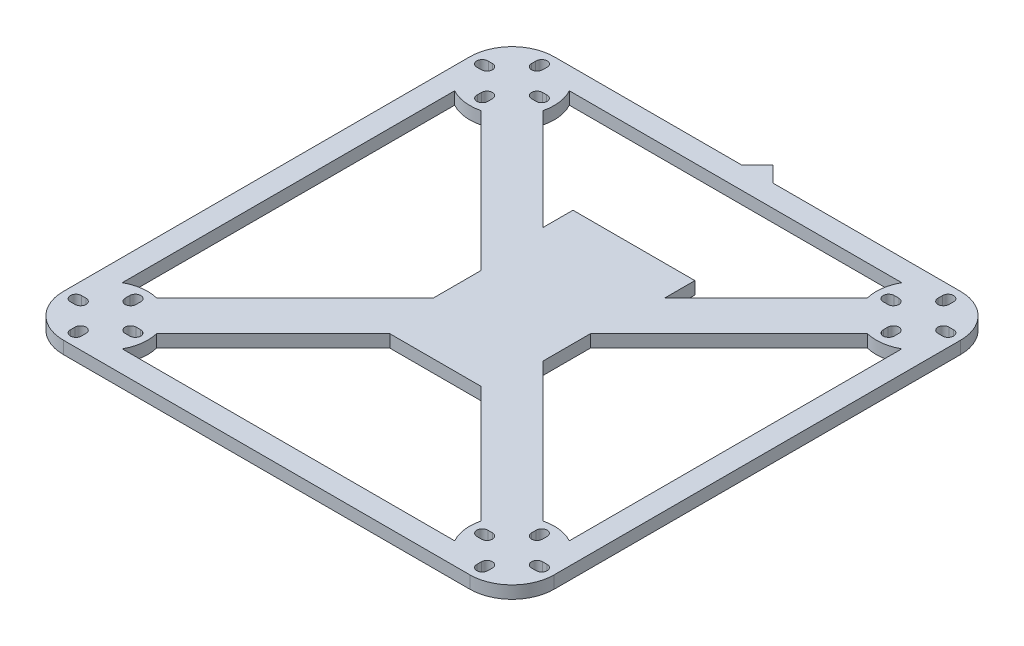
SolidWorks part; units mm, degrees
ref_plane "Front Plane" through (0, 0, 0) normal (0, 0, 1) x (1, 0, 0)
ref_plane "Top Plane" through (0, 0, 0) normal (0, 1, 0) x (1, 0, 0)
ref_plane "Right Plane" through (0, 0, 0) normal (1, 0, 0) x (0, 0, -1)
sketch "Sketch1" plane through (0, 0, 0) normal (0, 1, 0) x (1, 0, 0)
  line L0 (0, 78.5) -> (0, -78.5) construction
  line L1 (-78.5, 78.5) -> (78.5, 78.5)
  line L2 (-78.5, 78.5) -> (-78.5, -78.5)
  line L3 (-78.5, -78.5) -> (78.5, -78.5)
  line L4 (78.5, 78.5) -> (78.5, -78.5)
  line L5 (-78.5, 78.5) -> (78.5, -78.5) construction
  line L6 (-78.5, -78.5) -> (78.5, 78.5) construction
  line L7 (78.5, 0) -> (-78.5, 0) construction
  line L8 (-1, 65) -> (-1, 0) construction
  line L9 (-83.4497, 73.5503) -> (73.5503, -83.4497)
  line L10 (-73.5503, 83.4497) -> (83.4497, -73.5503)
  line L11 (-73.5503, -83.4497) -> (83.4497, 73.5503)
  line L12 (-83.4497, -73.5503) -> (73.5503, 83.4497)
  line L13 (-53.1678, 71.5) -> (53.1678, 71.5)
  line L14 (-53.1678, -71.5) -> (53.1678, -71.5)
  line L15 (71.5, -53.1678) -> (71.5, 53.1678)
  line L16 (-71.5, -53.1678) -> (-71.5, 53.1678)
  circle A0 centre (-65, 65) radius 13.5
  circle A1 centre (-65, 65) radius 64
  circle A2 centre (65, 65) radius 13.5
  circle A3 centre (-65, -65) radius 13.5
  circle A4 centre (65, -65) radius 13.5
  point P0 (0, 0)
  dimension "D1" = 27
  dimension "D2" = 128
  dimension "D3" = 2
  dimension "D4" = 14
  dimension "D5" = 7
extrude "Base shape" add sketch "Sketch1" along normal blind 4 contours L12 A3 L11 L9 | A4 L10 L11 L9 | L11 A2 L12 L10 | L9 A1 L10 A0 | A1 L9 L12 L10 | L12 L9 L11 L10 | L13 A1 L1 A0 | L13 A2 L1 A1 | A4 L4 A2 L15 | A4 L14 A3 L3 | L2 A3 L16 A1 | L2 A1 L16 A0 | A0 | A2 | A4 | A3 region at (-29.268, 0, -75.0845) region at (-75.0845, 0, -29.268) region at (27.4447, 0, -75.1014) region at (-37.8705, 0, -37.8705) region at (-75.1014, 0, 27.4447) region at (-12.3929, 0, -12.3929) region at (30.427, 0, -30.427) region at (0, 0, 0) region at (-30.427, 0, 30.427) region at (30.427, 0, 30.427) region at (75.0932, 0, 0) region at (0, 0, 75.0932)
sketch "Sketch2" plane through (0, 4, 0) normal (0, 1, 0) x (1, 0, 0)
  line L0 (-65, 74.5) -> (-65, 55.5) construction
  line L1 (-74.5, 65) -> (-55.5, 65) construction
  line L2 (0, 78.5) -> (0, -78.5) construction
  line L3 (-65, 78.5) -> (65, 78.5) construction
  line L4 (-65, -78.5) -> (65, -78.5) construction
  line L5 (-78.5, 0) -> (78.5, 0) construction
  line L6 (-78.5, 65) -> (-78.5, -65) construction
  line L7 (78.5, 65) -> (78.5, -65) construction
  line L8 (-66.75, 74.5) -> (-66.75, 73)
  line L9 (-63.25, 74.5) -> (-63.25, 73)
  line L10 (-74.5, 66.75) -> (-73, 66.75)
  line L11 (-74.5, 63.25) -> (-73, 63.25)
  line L12 (-66.75, 57) -> (-66.75, 55.5)
  line L13 (-63.25, 57) -> (-63.25, 55.5)
  line L14 (-57, 66.75) -> (-55.5, 66.75)
  line L15 (-57, 63.25) -> (-55.5, 63.25)
  line L16 (63.25, 57) -> (63.25, 55.5)
  line L17 (66.75, 57) -> (66.75, 55.5)
  line L18 (74.5, 63.25) -> (73, 63.25)
  line L19 (74.5, 66.75) -> (73, 66.75)
  line L20 (63.25, 74.5) -> (63.25, 73)
  line L21 (66.75, 74.5) -> (66.75, 73)
  line L22 (57, 66.75) -> (55.5, 66.75)
  line L23 (57, 63.25) -> (55.5, 63.25)
  line L24 (-66.75, -57) -> (-66.75, -55.5)
  line L25 (-63.25, -57) -> (-63.25, -55.5)
  line L26 (-57, -63.25) -> (-55.5, -63.25)
  line L27 (-57, -66.75) -> (-55.5, -66.75)
  line L28 (-74.5, -63.25) -> (-73, -63.25)
  line L29 (-74.5, -66.75) -> (-73, -66.75)
  line L30 (-63.25, -74.5) -> (-63.25, -73)
  line L31 (-66.75, -74.5) -> (-66.75, -73)
  line L32 (57, -63.25) -> (55.5, -63.25)
  line L33 (57, -66.75) -> (55.5, -66.75)
  line L34 (66.75, -74.5) -> (66.75, -73)
  line L35 (63.25, -74.5) -> (63.25, -73)
  line L36 (74.5, -66.75) -> (73, -66.75)
  line L37 (74.5, -63.25) -> (73, -63.25)
  line L38 (66.75, -57) -> (66.75, -55.5)
  line L39 (63.25, -57) -> (63.25, -55.5)
  circle A0 centre (-65, 65) radius 9.5
  circle A1 centre (-65, 65) radius 8
  circle A2 centre (-65, 74.5) radius 1.75
  circle A3 centre (-65, 55.5) radius 1.75
  circle A4 centre (-57, 65) radius 1.75
  circle A5 centre (-73, 65) radius 1.75
  circle A6 centre (-65, 73) radius 1.75
  circle A7 centre (-55.5, 65) radius 1.75
  circle A8 centre (-74.5, 65) radius 1.75
  circle A9 centre (-65, 57) radius 1.75
  circle A10 centre (65, 57) radius 1.75
  circle A11 centre (65, 55.5) radius 1.75
  circle A12 centre (73, 65) radius 1.75
  circle A13 centre (74.5, 65) radius 1.75
  circle A14 centre (65, 73) radius 1.75
  circle A15 centre (65, 74.5) radius 1.75
  circle A16 centre (57, 65) radius 1.75
  circle A17 centre (55.5, 65) radius 1.75
  circle A18 centre (-65, -57) radius 1.75
  circle A19 centre (-65, -55.5) radius 1.75
  circle A20 centre (-57, -65) radius 1.75
  circle A21 centre (-55.5, -65) radius 1.75
  circle A22 centre (-74.5, -65) radius 1.75
  circle A23 centre (-73, -65) radius 1.75
  circle A24 centre (-65, -74.5) radius 1.75
  circle A25 centre (-65, -73) radius 1.75
  circle A26 centre (55.5, -65) radius 1.75
  circle A27 centre (57, -65) radius 1.75
  circle A28 centre (65, -74.5) radius 1.75
  circle A29 centre (65, -73) radius 1.75
  circle A30 centre (74.5, -65) radius 1.75
  circle A31 centre (73, -65) radius 1.75
  circle A32 centre (65, -55.5) radius 1.75
  circle A33 centre (65, -57) radius 1.75
  dimension "D1" = 19
  dimension "D2" = 16
  dimension "D3" = 3.5
extrude "Motor mounting holes" cut sketch "Sketch2" against normal up to next contours A27 A26 | A26 A27 | A27 A26 | A27 L32 A26 | A27 A26 L33 | A29 A28 | A28 A29 | A28 A29 | A29 L35 A28 | A29 A28 L34 | A31 A30 | A30 A31 | A31 A30 | A31 A30 L37 | A31 L36 A30 | A33 A32 | A32 A33 | A33 A32 | A33 A32 L39 | A33 L38 A32 | A17 A16 | A17 A16 | A16 A17 | L22 A17 A16 | A16 A17 L23 | A11 A10 | A11 A10 | A10 A11 | L16 A11 A10 | A10 A11 L17 | A12 A13 | A13 A12 | A13 A12 | A12 A13 L19 | L18 A13 A12 | A14 A15 | A15 A14 | A15 A14 | A14 A15 L20 | L21 A15 A14 | A8 A5 L10 A0 | A8 A0 L11 A5 | A6 A2 A0 L8 | A6 L9 A0 A2 | A7 A4 L15 A0 | A7 A0 L14 A4 | A9 L12 A0 A3 | A9 A3 A0 L13 | A19 A18 | A19 A18 | A18 A19 | A18 A19 L24 | L25 A19 A18 | A22 A23 | A23 A22 | A23 A22 | A22 A23 L28 | L29 A23 A22 | A21 A20 | A21 A20 | A20 A21 | A20 A21 L26 | L27 A21 A20 | A24 A25 | A25 A24 | A25 A24 | A24 A25 L31 | L30 A25 A24 | A8 | A5 | A2 | A6 | A4 | A7 | A9 | A3 region at (-66.6996, 4, -73.7469) region at (-73.7469, 4, -66.6996) region at (-63.3004, 4, -73.7469) region at (-56.2531, 4, -66.6996) region at (-73.7469, 4, -63.3004) region at (-66.6996, 4, -56.2531) region at (-56.2531, 4, -63.3004) region at (-63.3004, 4, -56.2531) region at (63.3002, 4, -56.25) region at (65, 4, -57.6692) region at (65, 4, -54.8308) region at (66.6998, 4, -56.25) region at (65, 4, -56.25) region at (75.1692, 4, -65) region at (73.75, 4, -63.3002) region at (72.3308, 4, -65) region at (73.75, 4, -65) region at (73.75, 4, -66.6998) region at (63.3002, 4, -73.75) region at (65, 4, -75.1692) region at (65, 4, -72.3308) region at (66.6998, 4, -73.75) region at (65, 4, -73.75) region at (56.25, 4, -66.6998) region at (57.6692, 4, -65) region at (54.8308, 4, -65) region at (56.25, 4, -65) region at (56.25, 4, -63.3002) region at (-65, 4, 57.6692) region at (-66.6998, 4, 56.25) region at (-65, 4, 54.8308) region at (-63.3002, 4, 56.25) region at (-65, 4, 56.25) region at (-57.6692, 4, 65) region at (-56.25, 4, 63.3002) region at (-54.8308, 4, 65) region at (-56.25, 4, 66.6998) region at (-56.25, 4, 65) region at (-75.1692, 4, 65) region at (-73.75, 4, 63.3002) region at (-72.3308, 4, 65) region at (-73.75, 4, 66.6998) region at (-73.75, 4, 65) region at (-63.3002, 4, 73.75) region at (-65, 4, 75.1692) region at (-65, 4, 72.3308) region at (-66.6998, 4, 73.75) region at (-65, 4, 73.75) region at (56.25, 4, 63.3002) region at (57.6692, 4, 65) region at (54.8308, 4, 65) region at (56.25, 4, 65) region at (56.25, 4, 66.6998) region at (66.6998, 4, 73.75) region at (65, 4, 75.1692) region at (65, 4, 72.3308) region at (63.3002, 4, 73.75) region at (65, 4, 73.75) region at (75.1692, 4, 65) region at (73.75, 4, 66.6998)
sketch "Sketch3" plane through (0, 0, 0) normal (0, -1, 0) x (1, 0, 0)
  line L0 (0, -71.5) -> (0, -83.5) construction
  line L1 (-53.1678, -71.5) -> (53.1678, -71.5) construction
  line L2 (-65, -78.5) -> (65, -78.5) construction
  line L3 (0, -83.5) -> (-5, -78.5)
  line L4 (-5, -78.5) -> (5, -78.5)
  line L5 (0, -83.5) -> (5, -78.5)
  point P10 (0, -78.5)
  dimension "D1" = 5
  dimension "D2" = 45
extrude "Forward arrow" add sketch "Sketch3" against normal up to surface (4 mm away) contours L4 L0 L5 | L0 L4 L3 region at (1.6667, 0, -80.1667) region at (-1.6667, 0, -80.1667) up to face at (65, 4, 73.75)
sketch "Sketch4" plane through (0, 0, 0) normal (0, -1, 0) x (1, 0, 0)
  line L4 (17.5, 10.25) -> (19.5, 10.25)
  line L5 (17.5, 10.25) -> (19.5, 10.25)
  line L6 (-19.5, -39) -> (19.5, -39)
  line L7 (19.5, 10.25) -> (19.5, 24.5)
  line L8 (19.5, 10.25) -> (19.5, 24.5)
  line L9 (19.5, 24.5) -> (-19.5, 24.5)
  line L10 (-19.5, -39) -> (19.5, -39)
  line L11 (19.5, 24.5) -> (-19.5, 24.5)
  line L36 (-19.5, 24.5) -> (-19.5, 10.25)
  line L37 (-19.5, 24.5) -> (-19.5, 10.25)
  line L38 (-19.5, 10.25) -> (-17.5, 10.25)
  line L39 (-19.5, 10.25) -> (-17.5, 10.25)
  line L40 (-17.5, 10.25) -> (-17.5, -10.25)
  line L41 (-17.5, 10.25) -> (-17.5, -10.25)
  line L42 (-17.5, -10.25) -> (-19.5, -10.25)
  line L43 (-17.5, -10.25) -> (-19.5, -10.25)
  line L44 (-19.5, -10.25) -> (-19.5, -39)
  line L45 (-19.5, -10.25) -> (-19.5, -39)
  line L46 (19.5, -39) -> (19.5, -10.25)
  line L47 (19.5, -39) -> (19.5, -10.25)
  line L48 (19.5, -10.25) -> (17.5, -10.25)
  line L49 (19.5, -10.25) -> (17.5, -10.25)
  line L50 (17.5, -10.25) -> (17.5, 10.25)
  line L51 (17.5, -10.25) -> (17.5, 10.25)
  dimension "D1" = 0
extrude "Boss-Extrude1" add sketch "Sketch4" against normal up to surface (4 mm away) up to face at (65, 4, 73.75)
equation "\"MotorDiameter\"=27"
equation "\"D1@Sketch1\"=\"MotorDiameter\""
equation "\"PropDiameter\"=128"
equation "\"D2@Sketch1\"=\"PropDiameter\""
equation "\"PropDistance\"=2"
equation "\"D3@Sketch1\"=\"PropDistance\""
equation "\"ArmWidth\"=14"
equation "\"D4@Sketch1\"=\"ArmWidth\""
equation "\"FrameDepth\"=4"
equation "\"D1@Base shape\" = \"FrameDepth\""
equation "\"D5@Sketch1\"=\"ArmWidth\"/2"
equation "\"MotorHoleOuterDiameter\"=19"
equation "\"D1@Sketch2\"=\"MotorHoleOuterDiameter\""
equation "\"MotorHoleInnerDiameter\"=16"
equation "\"D2@Sketch2\"=\"MotorHoleInnerDiameter\""
equation "\"MotorHoleDiameter\"=3.5"
equation "\"D3@Sketch2\"=\"MotorHoleDiameter\""
